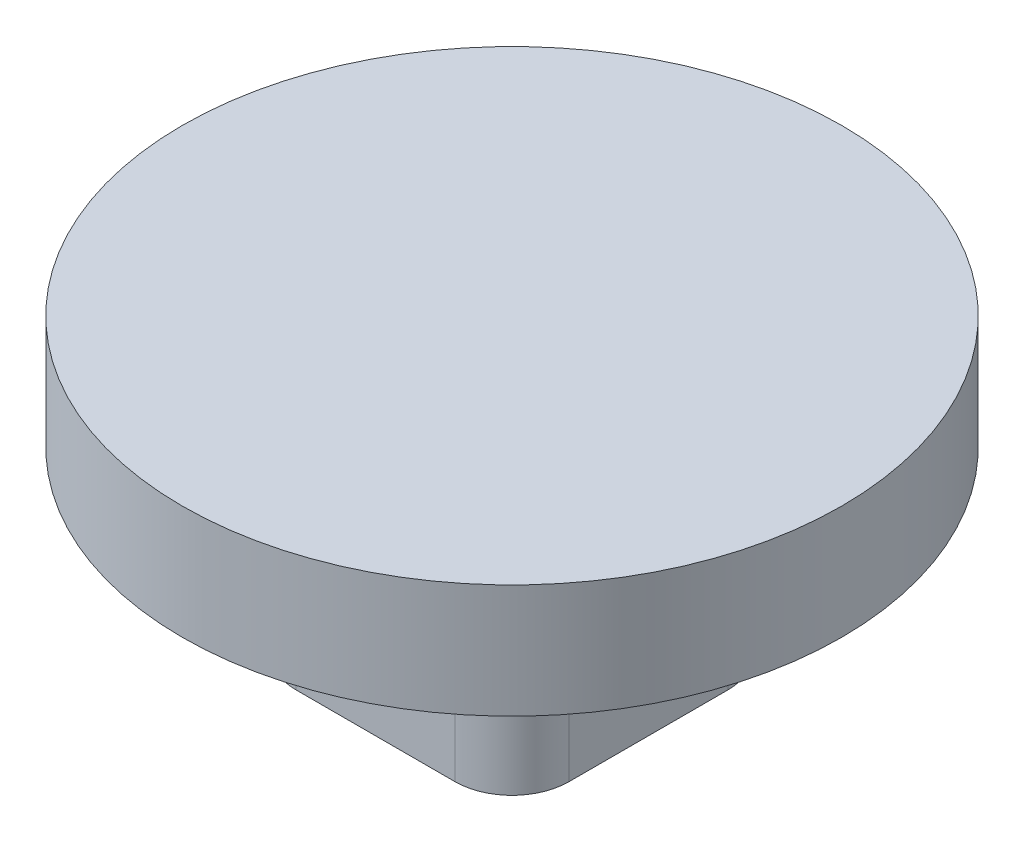
SolidWorks part; units mm, degrees
ref_plane "Front Plane" through (0, 0, 0) normal (0, 0, 1) x (1, 0, 0)
ref_plane "Top Plane" through (0, 0, 0) normal (0, 1, 0) x (1, 0, 0)
ref_plane "Right Plane" through (0, 0, 0) normal (1, 0, 0) x (0, 0, -1)
sketch "Sketch1" plane through (0, 0, 0) normal (0, 1, 0) x (1, 0, 0)
  circle A0 centre (0, 0) radius 29
  dimension "D1" = 58
extrude "Boss-Extrude1" add sketch "Sketch1" along normal blind 10
sketch "Sketch2" plane through (0, 0, 0) normal (0, -1, 0) x (1, 0, 0)
  line L5 (-10, -10) -> (10, 10) construction
  line L6 (-10, 10) -> (10, -10) construction
  line L7 (-12, -12) -> (12, -12)
  line L8 (-12, -12) -> (-12, 12)
  line L9 (-12, 12) -> (12, 12)
  line L10 (12, -12) -> (12, 12)
  line L11 (-12, -12) -> (12, 12) construction
  line L12 (-12, 12) -> (12, -12) construction
  circle A1 centre (0, 0) radius 10
  point P0 (0, 0)
  dimension "D1" = 20
  dimension "D2" = 24
extrude "Boss-Extrude2" add sketch "Sketch2" along normal blind 16
sketch "Sketch3" plane through (12, 0, 0) normal (1, 0, 0) x (0, 0, -1)
  line L0 (12, -16) -> (-12, -16) construction
  circle A0 centre (0, -8) radius 3
  dimension "D1" = 6
  dimension "D2" = 8
extrude "Cut-Extrude1" cut sketch "Sketch3" against normal through all
fillet "Fillet1" radius 5 4 edges at (-12, -8, -12) (12, -8, -12) (12, -8, 12) (-12, -8, 12)
fillet "Fillet2" radius 2 8 edges at (-10.5355, 0, 10.5355) (0, 0, 12) (10.5355, 0, 10.5355) (12, 0, 0) (10.5355, 0, -10.5355) (0, 0, -12) (-10.5355, 0, -10.5355) (-12, 0, 0)
